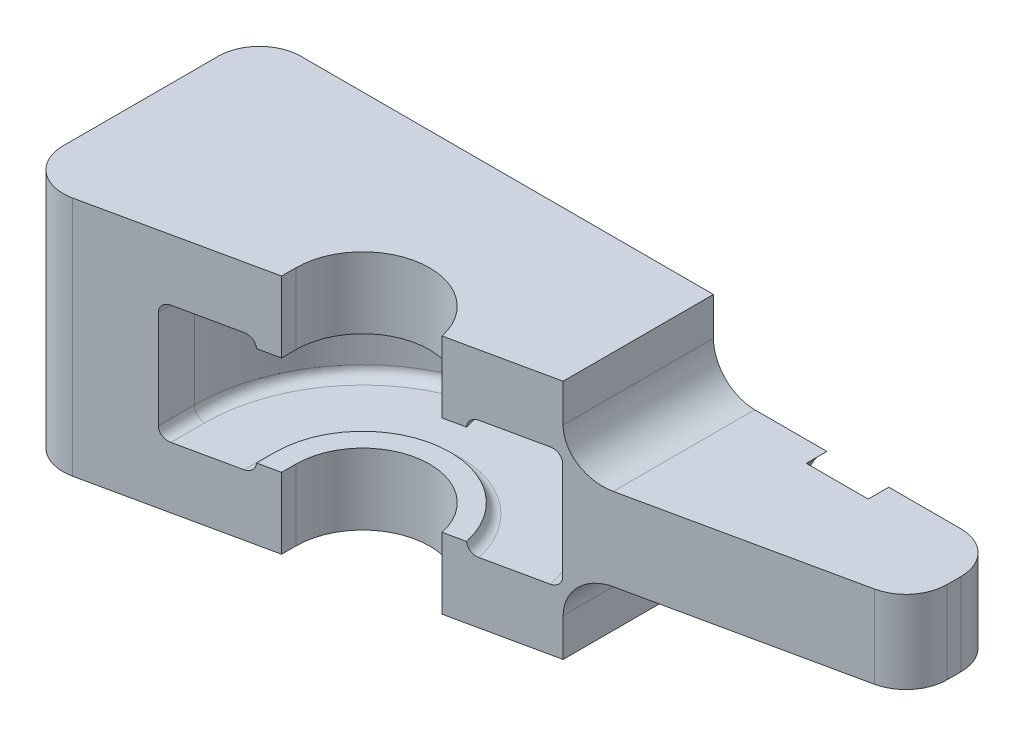
SolidWorks part; units mm, degrees
material "ABS"
ref_plane "Front" through (0, 0, 0) normal (0, 0, 1) x (1, 0, 0)
ref_plane "Top" through (0, 0, 0) normal (0, 1, 0) x (1, 0, 0)
ref_plane "Right" through (0, 0, 0) normal (1, 0, 0) x (0, 0, -1)
sketch "Sketch1" plane through (0, 0, 0) normal (0, 0, 1) x (1, 0, 0)
  line L0 (6.35, 0) -> (0, 0) construction
  line L1 (-22.225, 9.271) -> (34.925, 9.271)
  line L2 (-22.225, 9.271) -> (-22.225, -9.271)
  line L3 (-22.225, -9.271) -> (34.925, -9.271)
  line L4 (34.925, 9.271) -> (34.925, -9.271)
  line L5 (-22.225, 9.271) -> (34.925, -9.271) construction
  line L6 (-22.225, -9.271) -> (34.925, 9.271) construction
  dimension "D1" = 18.542
  dimension "D2" = 57.15
  dimension "D3" = 6.35
extrude "Boss-Extrude1" add sketch "Sketch1" along normal blind 19.05
sketch "Sketch3" plane through (0, 0, 0) normal (0, 1, 0) x (1, 0, 0)
  line L0 (0, 0) -> (0, -19.05) construction
  line L1 (34.925, -19.05) -> (-22.225, -19.05) construction
  line L2 (-22.225, -25.4) -> (34.925, -25.4) construction
  line L3 (-22.225, -19.05) -> (-22.225, 0) construction
  line L5 (0, -19.05) -> (0, -14.2875) construction
  line L6 (-5.1435, -19.05) -> (-5.1435, -14.2875)
  line L7 (5.1435, -19.05) -> (5.1435, -14.2875)
  line L8 (34.925, -19.05) -> (34.925, 0) construction
  circle A0 centre (0, -14.2875) radius 11.1125 construction
  arc A2 (-5.1435, -19.05) -> (5.1435, -19.05) centre (0, -19.05) ccw
  arc A3 (5.1435, -14.2875) -> (-5.1435, -14.2875) centre (0, -14.2875) ccw
  point P13 (0, -16.6687)
  dimension "D1" = 22.225
  dimension "D3" = 5.1435
  dimension "D2" = 6.35
extrude "Cut-Extrude1" cut sketch "Sketch3" along normal through all both and the other way through all
sketch "Sketch5" plane through (0, 0, 0) normal (0, 1, 0) x (1, 0, 0)
  line L0 (5.1435, -19.05) -> (-5.1435, -19.05) construction
  line L1 (0, -14.2875) -> (0, -19.05) construction
  line L2 (12.954, -14.2875) -> (12.954, -19.05)
  line L3 (-12.954, -14.2875) -> (-12.954, -19.05)
  line L4 (0, -19.05) -> (0, -14.2875) construction
  line L5 (-6.731, -19.05) -> (-6.731, -14.2875)
  line L6 (6.731, -19.05) -> (6.731, -14.2875)
  arc A0 (12.954, -14.2875) -> (-12.954, -14.2875) centre (0, -14.2875) ccw
  arc A1 (-12.954, -19.05) -> (12.954, -19.05) centre (0, -19.05) ccw
  arc A2 (-6.731, -19.05) -> (6.731, -19.05) centre (0, -19.05) ccw
  arc A3 (6.731, -14.2875) -> (-6.731, -14.2875) centre (0, -14.2875) ccw
  arc A4 (5.1435, -14.2875) -> (-5.1435, -14.2875) centre (0, -14.2875) ccw construction
  point P7 (0, -16.6687)
  point P12 (0, -16.6687)
  dimension "D1" = 12.954
  dimension "D2" = 1.5875
extrude "Cut-Extrude2" cut sketch "Sketch5" against normal blind 4.572 and the other way blind 4.572
sketch "Sketch6" plane through (0, 0, 0) normal (0, 1, 0) x (1, 0, 0)
  line L0 (-5.1435, -19.05) -> (5.1435, -19.05) construction
  line L1 (0, -19.05) -> (0, -14.2875) construction
  line L2 (-8.3185, -19.05) -> (-8.3185, -14.2875)
  line L3 (8.3185, -19.05) -> (8.3185, -14.2875)
  arc A0 (-8.3185, -19.05) -> (8.3185, -19.05) centre (0, -19.05) ccw
  arc A1 (8.3185, -14.2875) -> (-8.3185, -14.2875) centre (0, -14.2875) ccw
  arc A2 (5.1435, -14.2875) -> (-5.1435, -14.2875) centre (0, -14.2875) ccw construction
  point P7 (0, -16.6687)
  dimension "D1" = 3.175
extrude "Cut-Extrude3" cut sketch "Sketch6" against normal blind 3.81 and the other way blind 3.81
sketch "Sketch7" plane through (0, 0, 0) normal (0, 0, -1) x (-1, 0, 0)
  line L0 (0, 0) -> (-34.925, 0) construction
  line L1 (-34.925, -9.271) -> (-34.925, 9.271) construction
  line L3 (-13.1108, 0) -> (-16.0804, 5.1435)
  line L4 (-16.0804, 5.1435) -> (-22.0196, 5.1435)
  line L5 (-22.0196, 5.1435) -> (-24.9892, 0)
  line L6 (-24.9892, 0) -> (-22.0196, -5.1435)
  line L7 (-22.0196, -5.1435) -> (-16.0804, -5.1435)
  line L8 (-16.0804, -5.1435) -> (-13.1108, 0)
  circle A0 centre (-19.05, 0) radius 5.1435 construction
  dimension "D1" = 10.287
  dimension "D2" = 19.05
extrude "Cut-Extrude4" [suppressed] cut sketch "Sketch7" against normal blind 6.35
sketch "Sketch8" plane through (0, -9.271, 0) normal (0, -1, 0) x (1, 0, 0)
  line L0 (-22.225, 19.05) -> (34.925, 19.05)
  line L1 (34.925, 19.05) -> (34.925, 6.8036)
  line L2 (34.925, 19.05) -> (34.925, 0) construction
  line L3 (34.925, 6.8036) -> (-22.225, 19.05)
  point P4 (0, 14.2875)
extrude "Cut-Extrude5" cut sketch "Sketch8" against normal through all
fillet "Fillet1" radius 3.175 4 edges at (-22.225, 0, 0) (34.925, 0, 0) (34.925, 0, 6.8036) (-22.225, 0, 19.05)
sketch "Sketch9" plane through (0, 0, 0) normal (0, 0, -1) x (-1, 0, 0)
  line L0 (0, 0) -> (-34.925, 0) construction
  line L1 (-34.925, -9.271) -> (-34.925, 9.271) construction
  circle A0 centre (-23.8125, 0) radius 3.9688
  dimension "D1" = 7.9375
  dimension "D2" = 23.8125
extrude "Cut-Extrude6" cut sketch "Sketch9" against normal blind 1.5875
sketch "Sketch10" plane through (0, 0, 0) normal (0, 0, -1) x (-1, 0, 0)
  line L1 (-34.925, 9.271) -> (-12.7, 9.271)
  line L2 (-34.925, 9.271) -> (-34.925, 3.175)
  line L3 (-34.925, 3.175) -> (-12.7, 3.175)
  line L4 (-12.7, 9.271) -> (-12.7, 3.175)
  line L5 (-34.925, -9.271) -> (-12.7, -9.271)
  line L6 (-34.925, -9.271) -> (-34.925, -3.175)
  line L7 (-34.925, -3.175) -> (-12.7, -3.175)
  line L8 (-12.7, -9.271) -> (-12.7, -3.175)
  dimension "D1" = 6.35
  dimension "D2" = 22.225
extrude "Cut-Extrude7" cut sketch "Sketch10" against normal through all
fillet "Fillet2" radius 3.175 2 edges at (12.7, 3.175, 5.783) (12.7, -3.175, 5.783)
fillet "Fillet3" radius 0.7937 8 edges at (-6.731, 4.572, 15.0087) (-6.731, -4.572, 15.0087) (-12.954, -4.572, 15.6754) (-12.954, 4.572, 15.6754) (-0.7091, 4.572, 7.594) (-0.7091, -4.572, 7.594) (-1.3647, -4.572, 1.4056) (-1.3647, 4.572, 1.4056)
